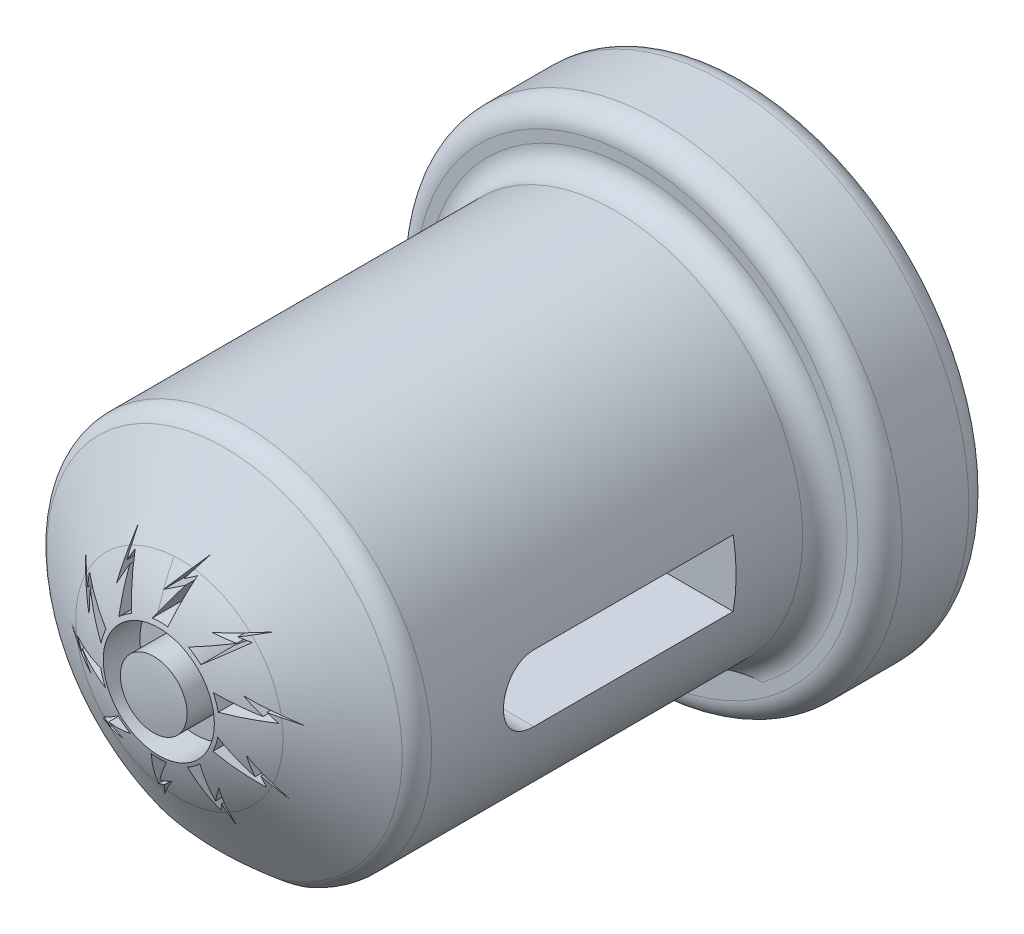
SolidWorks part; units mm, degrees
ref_plane "Alzado" through (0, 0, 0) normal (0, 0, 1) x (1, 0, 0)
ref_plane "Planta" through (0, 0, 0) normal (0, 1, 0) x (1, 0, 0)
ref_plane "Vista lateral" through (0, 0, 0) normal (1, 0, 0) x (0, 0, -1)
sketch "Croquis1" plane through (0, 0, 0) normal (0, 0, 1) x (1, 0, 0)
  line L0 (3.787, -7.6098) -> (-3.787, -7.6098)
  line L1 (3, -4.6098) -> (-3, -4.6098)
  arc A0 (3, -4.6098) -> (-3, -4.6098) centre (0, 0) ccw
  arc A1 (3.787, -7.6098) -> (-3.787, -7.6098) centre (0, 0) ccw
  point P7 (0, -4.6098)
  dimension "D1" = 11
  dimension "D2" = 6
  dimension "D3" = 3
extrude "Saliente-Extruir1" add sketch "Croquis1" along normal blind 23.3
sketch "Croquis2" plane through (0, 0, 0) normal (0, 0, -1) x (-1, 0, 0)
  line L0 (3, -4.6098) -> (-3, -4.6098) construction
  line L1 (3, -4.6098) -> (-3, -4.6098)
  circle A0 centre (0, 0) radius 11
  arc A1 (3, -4.6098) -> (-3, -4.6098) centre (0, 0) ccw construction
  arc A2 (3, -4.6098) -> (-3, -4.6098) centre (0, 0) ccw
  dimension "D1" = 22
extrude "Saliente-Extruir2" add sketch "Croquis2" against normal blind 5
sketch "Croquis3" plane through (0, 0, 0) normal (1, 0, 0) x (0, 0, -1)
  line L0 (-23.3, 0) -> (-23.3, 8.5)
  line L2 (-23.3, 8.5) -> (-25.6252, 4.6757)
  line L3 (-26.9351, 0) -> (-23.3, 0)
  arc A0 (-25.6252, 4.6757) -> (-26.9351, 0) centre (-17.9351, 0) ccw
  dimension "D2" = 9
  dimension "D1" = 31.3
revolve "Revolución1" add sketch "Croquis3" angle 360 about L3
sketch "Croquis4" plane through (0, 0, 23.3) normal (0, 0, -1) x (-1, 0, 0)
  line L1 (3.787, -7.6098) -> (-3.787, -7.6098)
  line L2 (3.787, -7.6098) -> (-3.787, -7.6098)
  arc A1 (-3.787, -7.6098) -> (3.787, -7.6098) centre (0, 0) ccw
  arc A2 (-3.787, -7.6098) -> (3.787, -7.6098) centre (0, 0) ccw
  dimension "D1" = 0
extrude "Cortar-Extruir1" cut sketch "Croquis4" against normal up to next
fillet "Redondeo3" radius 1 4 edges at (-11, 0, 0) (-11, 0, 5) (0, 8.5, 5) (0, 8.5, 23.3)
fillet "Redondeo2" radius 1 2 edges at (0, -4.6098, 0) (0, 5.5, 0)
ref_plane "Plano1" through (0, 0, 26.9351) normal (0, 0, 1) x (1, 0, 0)
sketch "Croquis5" plane through (0, 0, 26.9351) normal (0, 0, 1) x (1, 0, 0)
  line L0 (1.3026, 2.3441) -> (2.8816, 2.9738)
  line L1 (-0.324, 2.662) -> (0.5833, 4.0996)
  line L2 (0.5833, 4.0996) -> (-0.19, 3.662)
  line L3 (-0.19, 3.662) -> (1.0396, 5.192)
  line L4 (1.0396, 5.192) -> (0.4463, 4.2519)
  line L5 (0.4463, 4.2519) -> (0.876, 4.4951)
  line L6 (0.876, 4.4951) -> (0.376, 2.662)
  line L7 (2.8816, 2.9738) -> (1.9987, 3.0743)
  line L8 (1.9987, 3.0743) -> (3.8929, 3.5894)
  line L9 (3.8929, 3.5894) -> (2.8603, 3.1775)
  line L10 (2.8603, 3.1775) -> (3.3508, 3.1217)
  line L11 (3.3508, 3.1217) -> (1.8689, 1.9326)
  line L12 (2.4316, 1.1308) -> (4.0792, 0.7121)
  line L13 (4.0792, 0.7121) -> (3.4241, 1.3124)
  line L14 (3.4241, 1.3124) -> (5.2592, 0.6157)
  line L15 (5.2592, 0.6157) -> (4.1817, 0.8895)
  line L16 (4.1817, 0.8895) -> (4.5457, 0.5559)
  line L17 (4.5457, 0.5559) -> (2.6479, 0.465)
  line L18 (2.6319, -0.5144) -> (3.7187, -1.8216)
  line L19 (3.7187, -1.8216) -> (3.5415, -0.9509)
  line L20 (3.5415, -0.9509) -> (4.6166, -2.5932)
  line L21 (4.6166, -2.5932) -> (3.9059, -1.7384)
  line L22 (3.9059, -1.7384) -> (4.0044, -2.2222)
  line L23 (4.0044, -2.2222) -> (2.4155, -1.1802)
  line L24 (1.8268, -1.9632) -> (1.9378, -3.6595)
  line L25 (1.9378, -3.6595) -> (2.3062, -2.8509)
  line L26 (2.3062, -2.8509) -> (2.2107, -4.8115)
  line L27 (2.2107, -4.8115) -> (2.1381, -3.7022)
  line L28 (2.1381, -3.7022) -> (1.9334, -4.1515)
  line L29 (1.9334, -4.1515) -> (1.2605, -2.3746)
  line L30 (0.324, -2.662) -> (-0.5833, -4.0996)
  line L31 (-0.5833, -4.0996) -> (0.19, -3.662)
  line L32 (0.19, -3.662) -> (-1.0396, -5.192)
  line L33 (-1.0396, -5.192) -> (-0.4463, -4.2519)
  line L34 (-0.4463, -4.2519) -> (-0.876, -4.4951)
  line L35 (-0.876, -4.4951) -> (-0.376, -2.662)
  line L36 (-1.3026, -2.3441) -> (-2.8816, -2.9738)
  line L37 (-2.8816, -2.9738) -> (-1.9987, -3.0743)
  line L38 (-1.9987, -3.0743) -> (-3.8929, -3.5894)
  line L39 (-3.8929, -3.5894) -> (-2.8603, -3.1775)
  line L40 (-2.8603, -3.1775) -> (-3.3508, -3.1217)
  line L41 (-3.3508, -3.1217) -> (-1.8689, -1.9326)
  line L42 (-2.4316, -1.1308) -> (-4.0792, -0.7121)
  line L43 (-4.0792, -0.7121) -> (-3.4241, -1.3124)
  line L44 (-3.4241, -1.3124) -> (-5.2592, -0.6157)
  line L45 (-5.2592, -0.6157) -> (-4.1817, -0.8895)
  line L46 (-4.1817, -0.8895) -> (-4.5457, -0.5559)
  line L47 (-4.5457, -0.5559) -> (-2.6479, -0.465)
  line L48 (-2.6319, 0.5144) -> (-3.7187, 1.8216)
  line L49 (-3.7187, 1.8216) -> (-3.5415, 0.9509)
  line L50 (-3.5415, 0.9509) -> (-4.6166, 2.5932)
  line L51 (-4.6166, 2.5932) -> (-3.9059, 1.7384)
  line L52 (-3.9059, 1.7384) -> (-4.0044, 2.2222)
  line L53 (-4.0044, 2.2222) -> (-2.4155, 1.1802)
  line L54 (-1.8268, 1.9632) -> (-1.9378, 3.6595)
  line L55 (-1.9378, 3.6595) -> (-2.3062, 2.8509)
  line L56 (-2.3062, 2.8509) -> (-2.2107, 4.8115)
  line L57 (-2.2107, 4.8115) -> (-2.1381, 3.7022)
  line L58 (-2.1381, 3.7022) -> (-1.9334, 4.1515)
  line L59 (-1.9334, 4.1515) -> (-1.2605, 2.3746)
  circle A0 centre (0.026, -0.0152) radius 1.5
  circle A1 centre (0.026, -0.0152) radius 2.5
  arc A2 (0.376, 2.662) -> (-0.324, 2.662) centre (0.026, -0.0152) ccw
  arc A3 (1.8689, 1.9326) -> (1.3026, 2.3441) centre (0.0121, -0.0276) ccw
  arc A4 (2.6479, 0.465) -> (2.4316, 1.1308) centre (-0.0064, -0.0294) ccw
  arc A5 (2.4155, -1.1802) -> (2.6319, -0.5144) centre (-0.0225, -0.02) ccw
  arc A6 (1.2605, -2.3746) -> (1.8268, -1.9632) centre (-0.03, -0.003) ccw
  arc A7 (-0.376, -2.662) -> (0.324, -2.662) centre (-0.026, 0.0152) ccw
  arc A8 (-1.8689, -1.9326) -> (-1.3026, -2.3441) centre (-0.0121, 0.0276) ccw
  arc A9 (-2.6479, -0.465) -> (-2.4316, -1.1308) centre (0.0064, 0.0294) ccw
  arc A10 (-2.4155, 1.1802) -> (-2.6319, 0.5144) centre (0.0225, 0.02) ccw
  arc A11 (-1.2605, 2.3746) -> (-1.8268, 1.9632) centre (0.03, 0.003) ccw
  point P1 (0.026, 2.6848)
  point P4 (0.026, -0.0152)
  point P11 (0.026, -0.0152)
  point P38 (0.026, -0.0152)
  point P91 (0, 0)
  dimension "D1" = 3
  dimension "D12" = 2.7
  dimension "D9" = 5
  dimension "D2" = 0.2
  dimension "D3" = 1.9
  dimension "D4" = 1.7
  dimension "D5" = 0.7
  dimension "D6" = 0.5
  dimension "D7" = 1
  dimension "D8" = 2.53
  dimension "D10" = 0.566
  dimension "D11" = 0.6637
  dimension "D13" = 0.026
  dimension "D14" = 10
  dimension "D15" = 0.0064
extrude "Cortar-Extruir2" cut sketch "Croquis5" against normal blind 2
chamfer "Chaflán1" distance 0.5 angle 45 1 edges at (0, 5.5, 23.3)
ref_plane "Plano2" through (8.5, 0, 0) normal (1, 0, 0) x (0, 0, -1)
sketch "Croquis6" plane through (8.5, 0, 0) normal (1, 0, 0) x (0, 0, -1)
  line L0 (-18, 0) -> (-5, 0) construction
  line L1 (-18, 1.5) -> (-5, 1.5) construction
  line L2 (-18, -1.5) -> (-5, -1.5) construction
  line L3 (-23.3, -4.6098) -> (-23.3, 5) construction
  line L4 (-9, -1.5) -> (-9, 1.5)
  line L5 (-9, 1.5) -> (-18, 1.5)
  line L6 (-18, -1.5) -> (-9, -1.5)
  line L8 (-5, -7.6098) -> (-5, -8.5) construction
  arc A0 (-18, 1.5) -> (-18, -1.5) centre (-18, 0) ccw construction
  arc A1 (-5, -1.5) -> (-5, 1.5) centre (-5, 0) ccw construction
  arc A2 (-18, 1.5) -> (-18, -1.5) centre (-18, 0) ccw
  point P3 (-11.5, 0)
  point P8 (-19.5, 0)
  point P11 (-3.5, 0)
  dimension "D1" = 3
  dimension "D2" = 3.8
  dimension "D3" = 16
  dimension "D4" = 4
extrude "Cortar-Extruir3" cut sketch "Croquis6" against normal up to next
